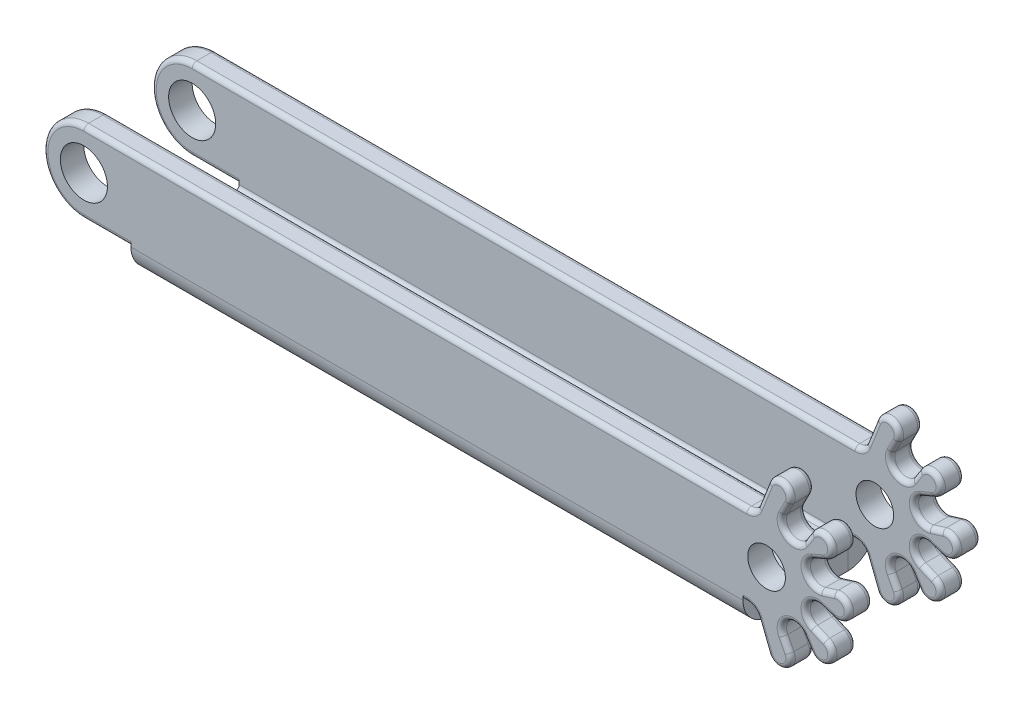
SolidWorks part; units mm, degrees
note: The reader was unsure of these and kept them because the rebuilt part matched: flange length of "Edge-Flange1".
ref_plane "Front Plane" through (0, 0, 0) normal (0, 0, 1) x (1, 0, 0)
ref_plane "Top Plane" through (0, 0, 0) normal (0, 1, 0) x (1, 0, 0)
ref_plane "Right Plane" through (0, 0, 0) normal (1, 0, 0) x (0, 0, -1)
sketch "Sketch1" plane through (0, 0, 0) normal (0, 1, 0) x (1, 0, 0)
  line L1 (-65, 14) -> (65, 14)
  line L2 (-65, 14) -> (-65, -14)
  line L3 (-65, -14) -> (65, -14)
  line L4 (65, 14) -> (65, -14)
  line L5 (-65, 14) -> (65, -14) construction
  line L6 (-65, -14) -> (65, 14) construction
  point P0 (0, 0)
  dimension "D1" = 28
  dimension "D2" = 130
base flange "Base-Flange1" sketch "Sketch1" thickness 5 reverse thickness direction no parameters "D1"=0.7366
edge flange "Edge-Flange1" sketch "Sketch10" flange profiles "Sketch10", "Sketch11" flange angle 90 flange length 23 flange position material inside bend radius 0.7366 thickness 5 parameters "D6"=10, "D8"=1
sketch "Sketch10" plane through (0, 0, 14) normal (0, 0, 1) x (1, 0, 0)
  line L0 (-65, 0) -> (65, 0) construction
  line L1 (-65, 0) -> (65, 0)
  line L2 (-65, 0) -> (-65, 18)
  line L3 (-65, 18) -> (65, 18)
  line L4 (65, 18) -> (65, 0)
sketch "Sketch11" plane through (0, 0, -14) normal (0, 0, -1) x (-1, 0, 0)
  line L0 (-65, 0) -> (65, 0) construction
  line L1 (-65, 0) -> (65, 0)
  line L2 (-65, 0) -> (-65, 18)
  line L3 (-65, 18) -> (65, 18)
  line L4 (65, 18) -> (65, 0)
bend "EdgeBend1" bend radius 0.7366 bend angle 90 parameters "D5"=1
bend "EdgeBend2" bend radius 0.7366 bend angle 90 parameters "D5"=2
sketch "Sketch15" plane through (0, 0, 14) normal (0, 0, 1) x (1, 0, 0)
  line L1 (-65, 18) -> (-65, 0.7366) construction
  line L2 (-75, 18) -> (-65, 18)
  line L3 (-65, 18) -> (-65, 0.7366)
  line L4 (-65, 0.7366) -> (-75, 0.7366)
  arc A0 (-75, 18) -> (-75, 0.7366) centre (-75, 9.3683) ccw
  circle A1 centre (-75, 9.3683) radius 5
  point P8 (-65, 9.3683)
  dimension "D1" = 10
  dimension "D2" = 10
extrude "Boss-Extrude1" add sketch "Sketch15" against normal blind 5 contours A1
mirror "Mirror3" about plane through (0, 0, 0) normal (0, 0, 1) of "Boss-Extrude1"
sketch "Sketch16" plane through (0, 0, 14) normal (0, 0, 1) x (1, 0, 0)
  line L0 (65, 18) -> (67.5, 18)
  line L1 (70, 9.3683) -> (91.4551, -27.793) construction
  line L2 (70, 9.3683) -> (91.4551, 46.5296) construction
  line L3 (35.0206, 9.3683) -> (142.7481, 9.3683) construction
  line L4 (70, 9.3683) -> (104.0826, -3.0368) construction
  line L5 (70, 9.3683) -> (104.0826, 21.7734) construction
  line L6 (70, 9.3683) -> (94.6256, -11.295) construction
  line L7 (70, 9.3683) -> (87.3049, 23.8889) construction
  line L16 (65, 18) -> (65, 0.7366)
  line L18 (65, 0.7366) -> (67.5, 0.7366)
  line L20 (70, 9.3683) -> (74.2698, -14.8467) construction
  line L21 (70, 9.3683) -> (74.0259, 32.2004) construction
  line L22 (73.5275, -1.7358) -> (74.8272, -4.259)
  line L23 (77.8527, 0.7613) -> (79.388, -1.6259)
  line L24 (79.8398, 3.1295) -> (82.4573, 2.032)
  line L25 (81.5479, 7.8226) -> (84.2585, 6.9808)
  line L26 (81.5479, 10.914) -> (84.2585, 11.7558)
  line L27 (79.8398, 15.6071) -> (82.4573, 16.7046)
  line L28 (77.8527, 17.9753) -> (79.388, 20.3625)
  line L29 (73.5275, 20.4724) -> (74.8272, 22.9956)
  line L30 (70.2786, 25.0564) -> (67.5, 18)
  line L31 (67.5, 0.7366) -> (70.2786, -6.3198)
  circle A0 centre (70, 9.3683) radius 17.5 construction
  circle A1 centre (70, 9.3683) radius 14 construction
  circle A2 centre (70, 9.3683) radius 15 construction
  circle A7 centre (70, 9.3683) radius 11.5 construction
  arc A11 (84.2585, 6.9808) -> (84.2585, 11.7558) centre (85, 9.3683) ccw
  arc A12 (79.8398, 15.6071) -> (81.5479, 10.914) centre (80.8065, 13.3015) ccw
  arc A13 (82.4573, 16.7046) -> (79.388, 20.3625) centre (81.4907, 19.0101) ccw
  arc A14 (73.5275, 20.4724) -> (77.8527, 17.9753) centre (75.75, 19.3276) ccw
  arc A15 (81.5479, 7.8226) -> (79.8398, 3.1295) centre (80.8065, 5.4351) ccw
  arc A16 (79.388, -1.6259) -> (82.4573, 2.032) centre (81.4907, -0.2735) ccw
  arc A17 (77.8527, 0.7613) -> (73.5275, -1.7358) centre (75.75, -0.591) ccw
  arc A18 (70.2786, -6.3198) -> (74.8272, -4.259) centre (72.6047, -5.4038) ccw
  arc A19 (74.8272, 22.9956) -> (70.2786, 25.0564) centre (72.6047, 24.1404) ccw
  point P21 (65, 9.3683)
  dimension "D1" = 35
  dimension "D2" = 28
  dimension "D5" = 30
  dimension "D6" = 23
  dimension "D3" = 120
  dimension "D4" = 40
  dimension "D7" = 20
  dimension "D8" = 20
  dimension "D9" = 5
  dimension "D10" = 20
  dimension "D11" = 20
  dimension "D12" = 2.5
extrude "Boss-Extrude2" add sketch "Sketch16" against normal blind 5
sketch "Sketch17" plane through (0, 0, 14) normal (0, 0, 1) x (1, 0, 0)
  circle A0 centre (70, 9.3683) radius 4
  dimension "D1" = 8
extrude "Cut-Extrude2" cut sketch "Sketch17" against normal blind 5
mirror "Mirror5" about plane through (0, 0, 0) normal (0, 0, 1) of "Cut-Extrude2", "Boss-Extrude2"
fillet "Fillet3" radius 2.5 4 edges at (67.5, 0.7366, 11.5) (67.5, 18, 11.5) (67.5, 18, -11.5) (67.5, 0.7366, -11.5)
fillet "Fillet4" radius 1 100 edges at (74.5, 1.5741, 9) (74.1774, -2.9974, 9) (73.6364, -7.681, 9) (65.3988, 0.7366, 9) (69.2012, 22.3202, 9) (73.6364, 26.4176, 9) (74.1774, 21.734, 9) (74.5, 17.1625, 9) (78.6203, 19.1689, 9) (83.4058, 20.6171, 9) (81.1486, 16.1558, 9) (78.4572, 12.4465, 9) (82.9032, 11.3349, 9) (87.5, 9.3683, 9) (82.9032, 7.4017, 9) (78.4572, 6.2901, 9) (81.1486, 2.5808, 9) (83.4058, -1.8805, 9) (78.6203, -0.4323, 9) (74.5, 1.5741, 14) (78.6203, -0.4323, 14) (83.4058, -1.8805, 14) (81.1486, 2.5808, 14) (78.4572, 6.2901, 14) (82.9032, 7.4017, 14) (87.5, 9.3683, 14) (82.9032, 11.3349, 14) (78.4572, 12.4465, 14) (81.1486, 16.1558, 14) (83.4058, 20.6171, 14) (78.6203, 19.1689, 14) (74.5, 17.1625, 14) (74.1774, 21.734, 14) (73.6364, 26.4176, 14) (69.2012, 22.3202, 14) (65.3988, 0.7366, 14) (73.6364, -7.681, 14) (74.1774, -2.9974, 14) (74.5, 1.5741, -14) (78.6203, -0.4323, -14) (83.4058, -1.8805, -14) (81.1486, 2.5808, -14) (78.4572, 6.2901, -14) (82.9032, 7.4017, -14) (87.5, 9.3683, -14) (82.9032, 11.3349, -14) (78.4572, 12.4465, -14) (81.1486, 16.1558, -14) (83.4058, 20.6171, -14) (78.6203, 19.1689, -14) (74.5, 17.1625, -14) (74.1774, 21.734, -14) (73.6364, 26.4176, -14) (69.2012, 22.3202, -14) (65.3988, 0.7366, -14) (73.6364, -7.681, -14) (74.1774, -2.9974, -14) (74.5, 1.5741, -9) (78.6203, -0.4323, -9) (83.4058, -1.8805, -9) (81.1486, 2.5808, -9) (78.4572, 6.2901, -9) (82.9032, 7.4017, -9) (87.5, 9.3683, -9) (82.9032, 11.3349, -9) (78.4572, 12.4465, -9) (81.1486, 16.1558, -9) (83.4058, 20.6171, -9) (78.6203, 19.1689, -9) (74.5, 17.1625, -9) (74.1774, 21.734, -9) (73.6364, 26.4176, -9) (69.2012, 22.3202, -9) (65.3988, 0.7366, -9) (73.6364, -7.681, -9) (74.1774, -2.9974, -9) (69.2012, -3.5836, -14) (69.2012, -3.5836, -9) (69.2012, -3.5836, 14) (69.2012, -3.5836, 9) (-4.6012, 18, 9) (-4.6012, 18, 14) (67.2047, 0.303, -14) (67.2047, 0.303, -9) (67.2047, 0.303, 14) (67.2047, 0.303, 9) (67.2047, 18.4336, -14) (67.2047, 18.4336, -9) (67.2047, 18.4336, 14) (67.2047, 18.4336, 9) (-4.6012, 18, -14) (-4.6012, 18, -9) (-70, 0.7366, 9) (-83.6317, 9.3683, 9) (-70, 0.7366, 14) (-83.6317, 9.3683, 14) (-70, 0.7366, -9) (-83.6317, 9.3683, -9) (-70, 0.7366, -14) (-83.6317, 9.3683, -14)
sketch "Bend-Lines1" [suppressed] plane through (0, 0, 0) normal (0, 1, 0) x (1, 0, 0)
sketch "Bounding-Box1" [suppressed] plane through (0, 0, 0) normal (0, 1, 0) x (1, 0, 0)
sheet metal parameters "Sheet-Metal1" thickness 5 parameters "D1"=0.7366
flat pattern "Flat-Pattern1" [suppressed]
sketch "Bend-Lines2" plane through (0, 0, 0) normal (0, 1, 0) x (1, 0, 0)
sketch3d "Bounding-Box2" [suppressed]
  line L0 (-72.5, -19, 0) -> (72.5, -19, 0) construction
  line L1 (-72.5, 19, 0) -> (72.5, 19, 0) construction
  line L2 (-72.5, -19, 0) -> (-72.5, 19, 0) construction
  line L3 (72.5, -19, 0) -> (72.5, 19, 0) construction
sheet metal parameters "Sheet-Metal2" thickness 5 parameters "D1"=0.7366
flat pattern "Flat-Pattern1"
sketch "Bend-Lines2" plane through (0, 0, 0) normal (0, 1, 0) x (1, 0, 0)
  line L0 (72.5, 15.8054) -> (-72.5, 15.8054) construction
  line L1 (-72.5, -15.8054) -> (72.5, -15.8054) construction
  line L2 (72.5, 15.8054) -> (-72.5, 15.8054) construction
  line L3 (-72.5, -15.8054) -> (72.5, -15.8054) construction
sketch3d "Bounding-Box2" [suppressed]
  line L0 (72.5, -35.6108, 0) -> (-72.5, -35.6108, 0) construction
  line L1 (72.5, 35.6108, 0) -> (-72.5, 35.6108, 0) construction
  line L2 (72.5, -35.6108, 0) -> (72.5, 35.6108, 0) construction
  line L3 (-72.5, -35.6108, 0) -> (-72.5, 35.6108, 0) construction
bend of the flat pattern "Flatten-<EdgeBend1>1"
bend of the flat pattern "Flatten-<EdgeBend2>1"
sheet metal parameters "Sheet-Metal3" thickness 5 parameters "D1"=0.7366
flat pattern "Flat-Pattern1"
sketch "Bend-Lines2" plane through (0, 0, 0) normal (0, 1, 0) x (1, 0, 0)
  line L0 (67.5, 15.8054) -> (-67.5, 15.8054) construction
  line L1 (-67.5, -15.8054) -> (67.5, -15.8054) construction
  line L2 (67.5, 15.8054) -> (-67.5, 15.8054) construction
  line L3 (-67.5, -15.8054) -> (67.5, -15.8054) construction
sketch3d "Bounding-Box2" [suppressed]
  line L0 (-86.1316, -35.6108, 0) -> (67.5, -35.6108, 0) construction
  line L1 (-86.1316, 35.6108, 0) -> (67.5, 35.6108, 0) construction
  line L2 (-86.1316, -35.6108, 0) -> (-86.1316, 35.6108, 0) construction
  line L3 (67.5, -35.6108, 0) -> (67.5, 35.6108, 0) construction
bend of the flat pattern "Flatten-<EdgeBend1>1"
bend of the flat pattern "Flatten-<EdgeBend2>1"
sheet metal parameters "Sheet-Metal7" thickness 5 parameters "D1"=0.7366
flat pattern "Flat-Pattern1"
sketch "Bend-Lines2" plane through (0, 0, 0) normal (0, 1, 0) x (1, 0, 0)
  line L0 (67.5, 15.8054) -> (-67.5, 15.8054) construction
  line L1 (-67.5, -15.8054) -> (67.5, -15.8054) construction
  line L2 (67.5, 15.8054) -> (-67.5, 15.8054) construction
  line L3 (-67.5, -15.8054) -> (67.5, -15.8054) construction
sketch3d "Bounding-Box2" [suppressed]
  line L0 (-86.1316, -35.6108, 0) -> (67.5, -35.6108, 0) construction
  line L1 (-86.1316, 35.6108, 0) -> (67.5, 35.6108, 0) construction
  line L2 (-86.1316, -35.6108, 0) -> (-86.1316, 35.6108, 0) construction
  line L3 (67.5, -35.6108, 0) -> (67.5, 35.6108, 0) construction
bend of the flat pattern "Flatten-<EdgeBend1>1"
bend of the flat pattern "Flatten-<EdgeBend2>1"
sheet metal parameters "Sheet-Metal8" thickness 5 parameters "D1"=0.7366
flat pattern "Flat-Pattern1"
sketch "Bend-Lines2" plane through (0, 0, 0) normal (0, 1, 0) x (1, 0, 0)
  line L0 (67.5, 15.8054) -> (-67.5, 15.8054) construction
  line L1 (-67.5, -15.8054) -> (67.5, -15.8054) construction
  line L2 (67.5, 15.8054) -> (-67.5, 15.8054) construction
  line L3 (-67.5, -15.8054) -> (67.5, -15.8054) construction
sketch3d "Bounding-Box2" [suppressed]
  line L0 (-86.1316, -42.4695, 0) -> (84.0954, -42.4695, 0) construction
  line L1 (-86.1316, 35.6108, 0) -> (84.0954, 35.6108, 0) construction
  line L2 (-86.1316, -42.4695, 0) -> (-86.1316, 35.6108, 0) construction
  line L3 (84.0954, -42.4695, 0) -> (84.0954, 35.6108, 0) construction
bend of the flat pattern "Flatten-<EdgeBend1>1"
bend of the flat pattern "Flatten-<EdgeBend2>1"
sheet metal parameters "Sheet-Metal9" thickness 5 parameters "D1"=0.7366
flat pattern "Flat-Pattern1"
sketch "Bend-Lines2" plane through (0, 0, 0) normal (0, 1, 0) x (1, 0, 0)
  line L0 (67.5, 15.8054) -> (-67.5, 15.8054) construction
  line L1 (-67.5, -15.8054) -> (67.5, -15.8054) construction
  line L2 (67.5, 15.8054) -> (-67.5, 15.8054) construction
  line L3 (-67.5, -15.8054) -> (67.5, -15.8054) construction
sketch3d "Bounding-Box2" [suppressed]
  line L0 (-86.1316, -42.4695, 0) -> (84.0954, -42.4695, 0) construction
  line L1 (-86.1316, 35.6108, 0) -> (84.0954, 35.6108, 0) construction
  line L2 (-86.1316, -42.4695, 0) -> (-86.1316, 35.6108, 0) construction
  line L3 (84.0954, -42.4695, 0) -> (84.0954, 35.6108, 0) construction
bend of the flat pattern "Flatten-<EdgeBend1>1"
bend of the flat pattern "Flatten-<EdgeBend2>1"
sheet metal parameters "Sheet-Metal10" thickness 5 parameters "D1"=0.7366
flat pattern "Flat-Pattern1"
sketch "Bend-Lines2" plane through (0, 0, 0) normal (0, 1, 0) x (1, 0, 0)
  line L0 (65, 10.8054) -> (-65, 10.8054) construction
  line L1 (-65, -10.8054) -> (65, -10.8054) construction
  line L2 (65, 10.8054) -> (-65, 10.8054) construction
  line L3 (-65, -10.8054) -> (65, -10.8054) construction
sketch3d "Bounding-Box2" [suppressed]
  line L0 (-83.6317, -39.2513, 0) -> (87.5, -39.2513, 0) construction
  line L1 (-83.6317, 39.2513, 0) -> (87.5, 39.2513, 0) construction
  line L2 (-83.6317, -39.2513, 0) -> (-83.6317, 39.2513, 0) construction
  line L3 (87.5, -39.2513, 0) -> (87.5, 39.2513, 0) construction
bend of the flat pattern "Flatten-<EdgeBend1>1"
bend of the flat pattern "Flatten-<EdgeBend2>1"
